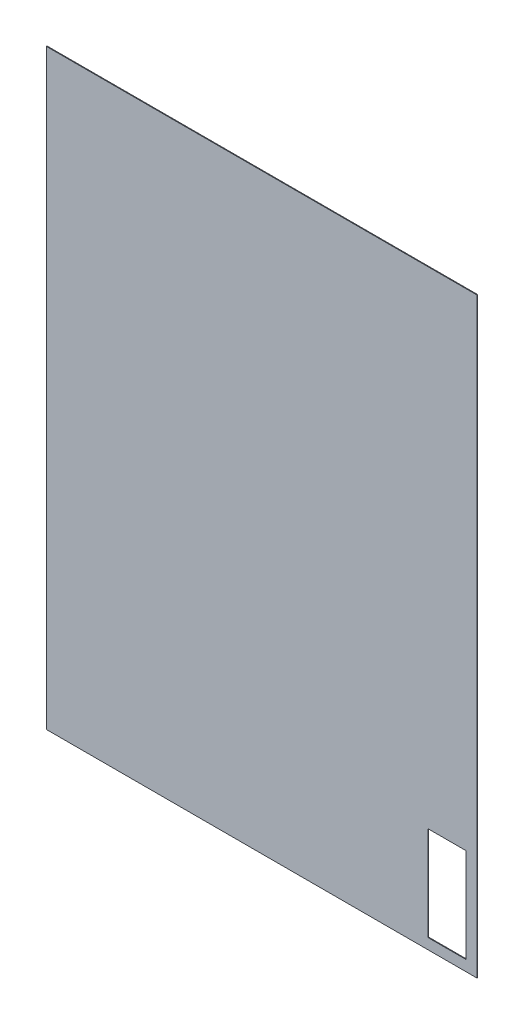
SolidWorks part; units mm, degrees
ref_plane "Front Plane" through (0, 0, 0) normal (0, 0, 1) x (1, 0, 0)
ref_plane "Top Plane" through (0, 0, 0) normal (0, 1, 0) x (1, 0, 0)
ref_plane "Right Plane" through (0, 0, 0) normal (1, 0, 0) x (0, 0, -1)
sketch "Sketch1" plane through (0, 0, 0) normal (0, 0, 1) x (1, 0, 0)
  line L1 (0, 0) -> (1215, 0)
  line L2 (0, 0) -> (0, 1670)
  line L3 (0, 1670) -> (1215, 1670)
  line L4 (1215, 0) -> (1215, 1670)
  line L5 (1185, 30) -> (1076.65, 30)
  line L6 (1185, 30) -> (1185, 296)
  line L7 (1185, 296) -> (1076.65, 296)
  line L8 (1076.65, 30) -> (1076.65, 296)
  dimension "D1" = 1215
  dimension "D2" = 1670
  dimension "D3" = 108.35
  dimension "D4" = 30
  dimension "D5" = 30
  dimension "D6" = 266
extrude "Boss-Extrude1" add sketch "Sketch1" along normal blind 2
